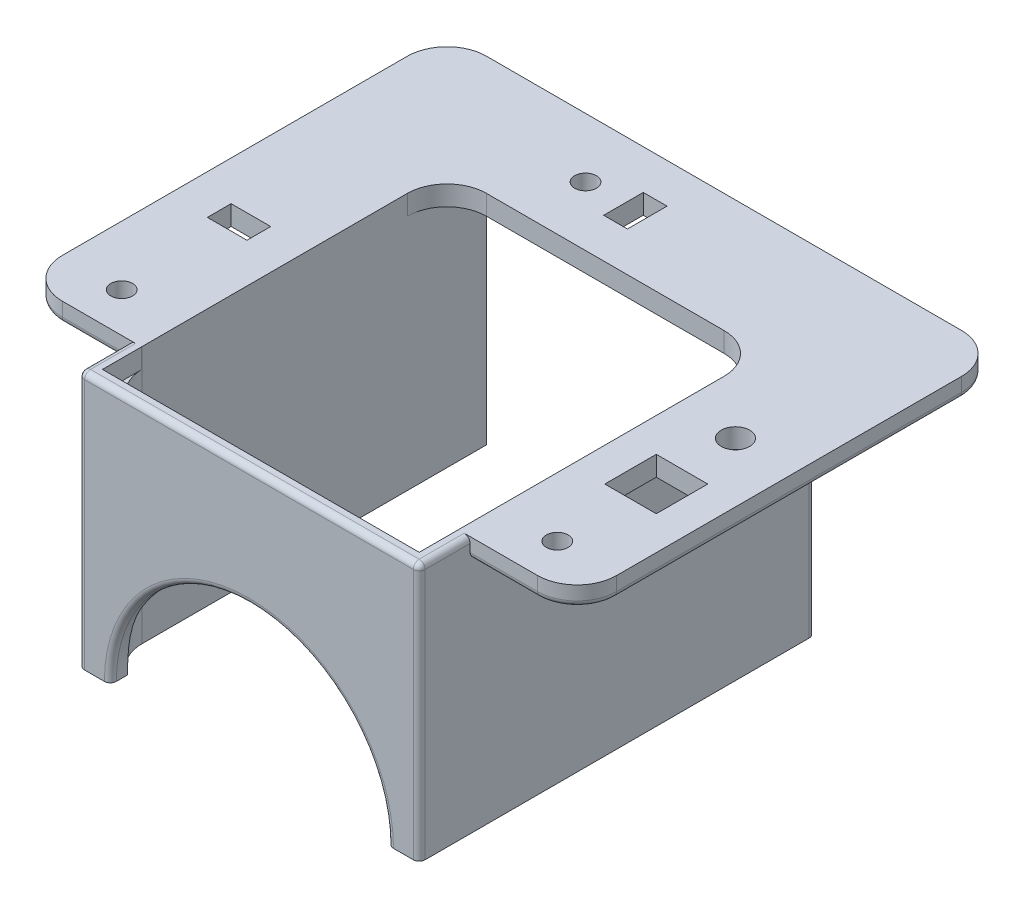
SolidWorks part; units mm, degrees
ref_plane "Front Plane" through (0, 0, 0) normal (0, 0, 1) x (1, 0, 0)
ref_plane "Top Plane" through (0, 0, 0) normal (0, 1, 0) x (1, 0, 0)
ref_plane "Right Plane" through (0, 0, 0) normal (1, 0, 0) x (0, 0, -1)
sketch "Sketch1" plane through (0, 0, 0) normal (0, 1, 0) x (1, 0, 0)
  line L0 (0, 0) -> (0, 100)
  line L1 (0, 100) -> (3, 100)
  line L2 (3, 100) -> (3, 3)
  line L3 (3, 3) -> (83, 3)
  line L4 (83, 3) -> (83, 100)
  line L5 (83, 100) -> (86, 100)
  line L6 (86, 100) -> (86, 0)
  line L7 (86, 0) -> (0, 0)
  dimension "D1" = 80
  dimension "D2" = 3
  dimension "D3" = 3
  dimension "D4" = 100
extrude "Boss-Extrude1" add sketch "Sketch1" along normal blind 60
sketch "Sketch2" plane through (0, 60, 0) normal (0, 1, 0) x (1, 0, 0)
  line L0 (0, 0) -> (86, 0) construction
  line L1 (83, 12.865) -> (113, 12.865)
  line L2 (83, 12.865) -> (83, 120)
  line L3 (83, 120) -> (113, 120)
  line L4 (113, 12.865) -> (113, 120)
  line L5 (3, 120) -> (-27, 120)
  line L6 (3, 120) -> (3, 12.865)
  line L7 (3, 12.865) -> (-27, 12.865)
  line L8 (-27, 120) -> (-27, 12.865)
  dimension "D1" = 30
  dimension "D2" = 12.865
  dimension "D3" = 12.865
  dimension "D4" = 107.135
  dimension "D5" = 107.135
extrude "Boss-Extrude2" add sketch "Sketch2" along normal blind 5
sketch "Sketch3" plane through (0, 65, 0) normal (0, 1, 0) x (1, 0, 0)
  line L1 (3, 120) -> (83, 120)
  line L2 (3, 120) -> (3, 90)
  line L3 (3, 90) -> (83, 90)
  line L4 (83, 120) -> (83, 90)
  dimension "D1" = 30
extrude "Boss-Extrude3" add sketch "Sketch3" against normal blind 5
sketch "Sketch5" plane through (0, 60, 0) normal (0, 1, 0) x (1, 0, 0)
  line L0 (0, 12.865) -> (0, 0)
  line L1 (0, 0) -> (86, 0)
  line L2 (86, 0) -> (86, 12.865)
  line L3 (86, 12.865) -> (83, 12.865)
  line L4 (83, 12.865) -> (83, 3)
  line L5 (83, 3) -> (3, 3)
  line L6 (83, 3) -> (3, 3) construction
  line L7 (3, 3) -> (3, 12.865)
  line L8 (3, 3) -> (3, 12.865) construction
  line L9 (0, 12.865) -> (3, 12.865) construction
  line L10 (0, 12.865) -> (3, 12.865)
fillet "Fillet2" radius 10 8 edges at (83, 30, -3) (3, 30, -3) (113, 62.5, -120) (-27, 62.5, -120) (113, 62.5, -12.865) (83, 62.5, -90) (3, 62.5, -90) (-27, 62.5, -12.865)
extrude "Boss-Extrude4" add sketch "Sketch5" along normal blind 5
sketch "Sketch6" plane through (0, 0, 0) normal (0, 0, 1) x (1, 0, 0)
  line L1 (8, 0) -> (78, 0)
  line L2 (0, 0) -> (86, 0) construction
  arc A0 (8, 0) -> (78, 0) centre (43, 0) cw
  dimension "D1" = 35
extrude "Cut-Extrude2" cut sketch "Sketch6" against normal blind 5 contours A0 L1
sketch "Sketch7" plane through (0, 65, 0) normal (0, 1, 0) x (1, 0, 0)
  line L1 (13, 90) -> (73, 90) construction
  line L2 (-17, 12.865) -> (0, 12.865) construction
  line L3 (86, 12.865) -> (103, 12.865) construction
  line L4 (83, 80) -> (83, 13) construction
  line L5 (-27, 110) -> (-27, 22.865) construction
  circle A0 centre (-12, 22.865) radius 2.75
  circle A1 centre (23, 105) radius 2.75
  circle A2 centre (98, 22.865) radius 2.75
  dimension "D1" = 5.5
  dimension "D2" = 5.5
  dimension "D3" = 5.5
  dimension "D4" = 50
  dimension "D5" = 15
  dimension "D6" = 10
  dimension "D7" = 10
  dimension "D8" = 15
extrude "Cut-Extrude3" cut sketch "Sketch7" against normal through all
sketch "Sketch8" plane through (0, 65, 0) normal (0, 1, 0) x (1, 0, 0)
  line L1 (-1.25, 49.5) -> (-22.75, 49.5) construction
  line L2 (-17, 49.5) -> (-7, 49.5)
  line L3 (-17, 49.5) -> (-17, 55.5)
  line L4 (-17, 55.5) -> (-7, 55.5)
  line L5 (32.5811, 100) -> (38.5811, 100)
  line L6 (32.5811, 100) -> (32.5811, 110)
  line L7 (32.5811, 110) -> (38.5811, 110)
  line L8 (38.5811, 100) -> (38.5811, 110)
  line L10 (98, 22.865) -> (98, 120) construction
  line L11 (103, 120) -> (-17, 120) construction
  line L12 (68.7464, 105) -> (18.6962, 105) construction
  line L13 (-7, 49.5) -> (-7, 55.5)
  line L14 (-12, 120) -> (-12, 12.865) construction
  line L17 (-12, 55.5) -> (-12, 49.5) construction
  line L19 (103, 120) -> (-17, 120) construction
  line L20 (-17, 12.865) -> (0, 12.865) construction
  line L21 (3, 13) -> (3, 80) construction
  dimension "D1" = 10
  dimension "D2" = 6
  dimension "D3" = 10
  dimension "D4" = 6
  dimension "D5" = 15
  dimension "D6" = 5
  dimension "D7" = 5
extrude "Cut-Extrude4" cut sketch "Sketch8" against normal through all
ref_plane "Plane1" through (43, 0, 0) normal (-1, 0, 0) x (0, 0, 1)
sketch "Sketch9" plane through (0, 65, 0) normal (0, 1, 0) x (1, 0, 0)
  line L0 (3, 80) -> (3, 120) construction
  line L1 (103, 120) -> (-17, 120) construction
  line L2 (-12, 120) -> (-12, 12.865) construction
  line L3 (-17, 12.865) -> (0, 12.865) construction
  line L5 (3, 13) -> (3, 80) construction
  dimension "D1" = 15
sketch "Sketch10" plane through (0, 65, 0) normal (0, 1, 0) x (1, 0, 0)
  line L0 (91.5, 41.365) -> (104.5, 54.365) construction
  line L1 (91.5, 41.365) -> (104.5, 41.365)
  line L2 (91.5, 41.365) -> (91.5, 54.365)
  line L3 (91.5, 54.365) -> (104.5, 54.365)
  line L4 (104.5, 41.365) -> (104.5, 54.365)
  line L5 (91.5, 41.365) -> (104.5, 54.365) construction
  line L6 (91.5, 54.365) -> (104.5, 41.365) construction
  line L7 (91.5, 54.365) -> (104.5, 41.365) construction
  line L8 (86, 12.865) -> (103, 12.865) construction
  circle A0 centre (98, 67.865) radius 3.585
  point P0 (98, 47.865)
  point P11 (94.5, 12.865)
  dimension "D2" = 7.17
  dimension "D1" = 13
  dimension "D3" = 55
extrude "Cut-Extrude5" cut sketch "Sketch10" against normal through all
fillet "Fillet3" radius 1.5 17 edges at (-8.5, 60, -12.865) (-24.0711, 60, -15.7939) (-27, 60, -66.4325) (-24.0711, 60, -117.0711) (43, 60, -120) (110.0711, 60, -117.0711) (113, 60, -66.4325) (94.5, 60, -12.865) (110.0711, 60, -15.7939) (0, 32.5, 0) (0, 65, -6.4325) (43, 65, 0) (86, 32.5, 0) (86, 65, -6.4325) (0, 30, -100) (86, 30, -100) (43, 35, 0)
